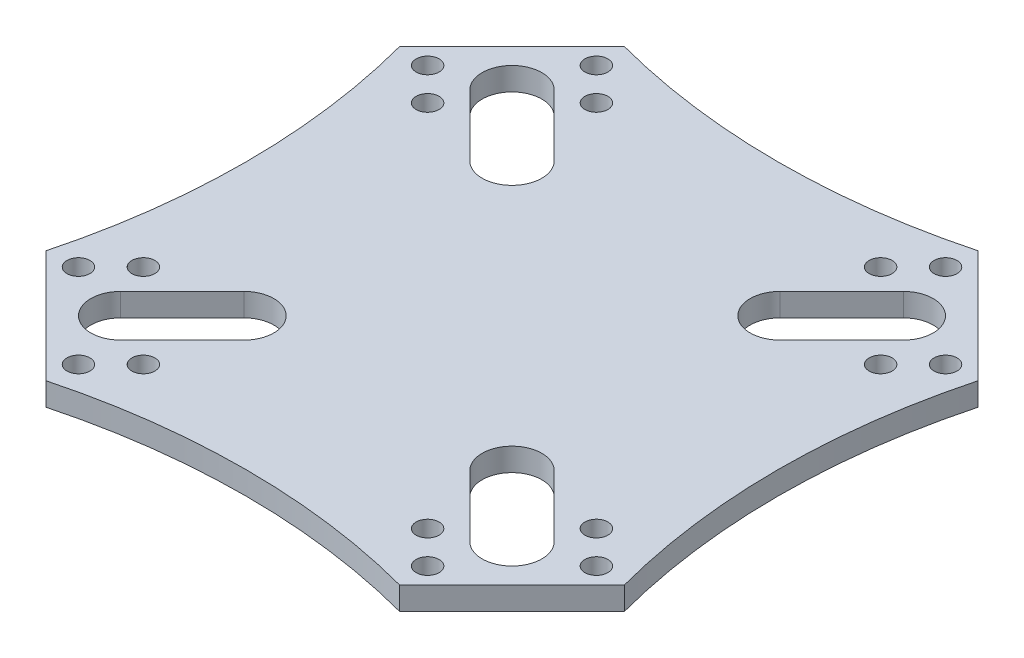
SolidWorks part; units mm, degrees
ref_plane "前视基准面" through (0, 0, 0) normal (0, 0, 1) x (1, 0, 0)
ref_plane "上视基准面" through (0, 0, 0) normal (0, 1, 0) x (1, 0, 0)
ref_plane "右视基准面" through (0, 0, 0) normal (1, 0, 0) x (0, 0, -1)
sketch "草图1" plane through (0, 0, 0) normal (0, 1, 0) x (1, 0, 0)
  line L0 (0, -72.2457) -> (0, 72.2457) construction
  line L1 (-102.9991, 0) -> (102.9991, 0) construction
  line L2 (38.5, 63.025) -> (63.025, 38.5)
  line L3 (50.7625, 50.7625) -> (0, 0) construction
  line L5 (63.025, -38.5) -> (38.5, -63.025)
  line L7 (-38.5, -63.025) -> (-63.025, -38.5)
  line L9 (-63.025, 38.5) -> (-38.5, 63.025)
  line L10 (29.1957, 29.1957) -> (42.6308, 42.6308) construction
  line L11 (24.5996, 33.7919) -> (38.0346, 47.227)
  line L12 (33.7919, 24.5996) -> (47.227, 38.0346)
  line L13 (29.1957, -29.1957) -> (42.6308, -42.6308) construction
  line L14 (33.7919, -24.5996) -> (47.227, -38.0346)
  line L15 (24.5996, -33.7919) -> (38.0346, -47.227)
  line L16 (-29.1957, -29.1957) -> (-42.6308, -42.6308) construction
  line L17 (-24.5996, -33.7919) -> (-38.0346, -47.227)
  line L18 (-33.7919, -24.5996) -> (-47.227, -38.0346)
  line L19 (-29.1957, 29.1957) -> (-42.6308, 42.6308) construction
  line L20 (-33.7919, 24.5996) -> (-47.227, 38.0346)
  line L21 (-24.5996, 33.7919) -> (-38.0346, 47.227)
  line L22 (0, 0) -> (29.1957, 29.1957) construction
  line L23 (0, 0) -> (38.5, 63.025) construction
  arc A0 (-38.5, 63.025) -> (38.5, 63.025) centre (0, 208) ccw
  arc A4 (24.5996, 33.7919) -> (33.7919, 24.5996) centre (29.1957, 29.1957) ccw
  arc A5 (47.227, 38.0346) -> (38.0346, 47.227) centre (42.6308, 42.6308) ccw
  arc A6 (33.7919, -24.5996) -> (24.5996, -33.7919) centre (29.1957, -29.1957) ccw
  arc A7 (38.0346, -47.227) -> (47.227, -38.0346) centre (42.6308, -42.6308) ccw
  arc A8 (-24.5996, -33.7919) -> (-33.7919, -24.5996) centre (-29.1957, -29.1957) ccw
  arc A9 (-47.227, -38.0346) -> (-38.0346, -47.227) centre (-42.6308, -42.6308) ccw
  arc A10 (-33.7919, 24.5996) -> (-24.5996, 33.7919) centre (-29.1957, 29.1957) ccw
  arc A11 (-38.0346, 47.227) -> (-47.227, 38.0346) centre (-42.6308, 42.6308) ccw
  arc A12 (63.025, 38.5) -> (63.025, -38.5) centre (208, 0) ccw
  arc A13 (38.5, -63.025) -> (-38.5, -63.025) centre (0, -208) ccw
  arc A14 (-63.025, -38.5) -> (-63.025, 38.5) centre (-208, 0) ccw
  point P13 (35.9133, 35.9133)
  point P33 (47.227, 47.227)
  point P34 (24.5996, 24.5996)
  point P37 (35.9133, -35.9133)
  point P46 (-35.9133, -35.9133)
  point P53 (-35.9133, 35.9133)
  dimension "D1" = 150
  dimension "D2" = 208
  dimension "D3" = 38.5
  dimension "D4" = 38.5
  dimension "D5" = 45
  dimension "D7" = 13
  dimension "D8" = 32
  dimension "D9" = 5
  dimension "D10" = 73.8539
  dimension "D11" = 4
  dimension "D13" = 45
  dimension "D6" = 4
extrude "凸台-拉伸2" add sketch "草图1" along normal mid plane 5
sketch "草图2" plane through (0, 2.5, 0) normal (0, 1, 0) x (1, 0, 0)
  line L0 (63.025, 38.5) -> (38.5, 63.025) construction
  line L1 (47.227, 47.227) -> (50.7625, 50.7625) construction
  circle A0 centre (38.0346, 56.4194) radius 2.5
  circle A1 centre (56.4194, 38.0346) radius 2.5
  arc A2 (47.227, 38.0346) -> (38.0346, 47.227) centre (42.6308, 42.6308) ccw construction
  dimension "D2" = 5
  dimension "D1" = 5
  dimension "D3" = 13
  dimension "D4" = 13
  dimension "D5" = 5
extrude "切除-拉伸1" cut sketch "草图2" against normal through all
pattern_linear "阵列(线性)1" count 2 spacing 10 along (-0.7071, 0, 0.7071) of "切除-拉伸1"
ref_axis "基准轴1" through (0, -113.174, 0) along (0, 1, 0)
pattern_circular "阵列(圆周)1" count 4 over 360 about axis through (0, -113.174, 0) along (0, 1, 0) of "阵列(线性)1"
